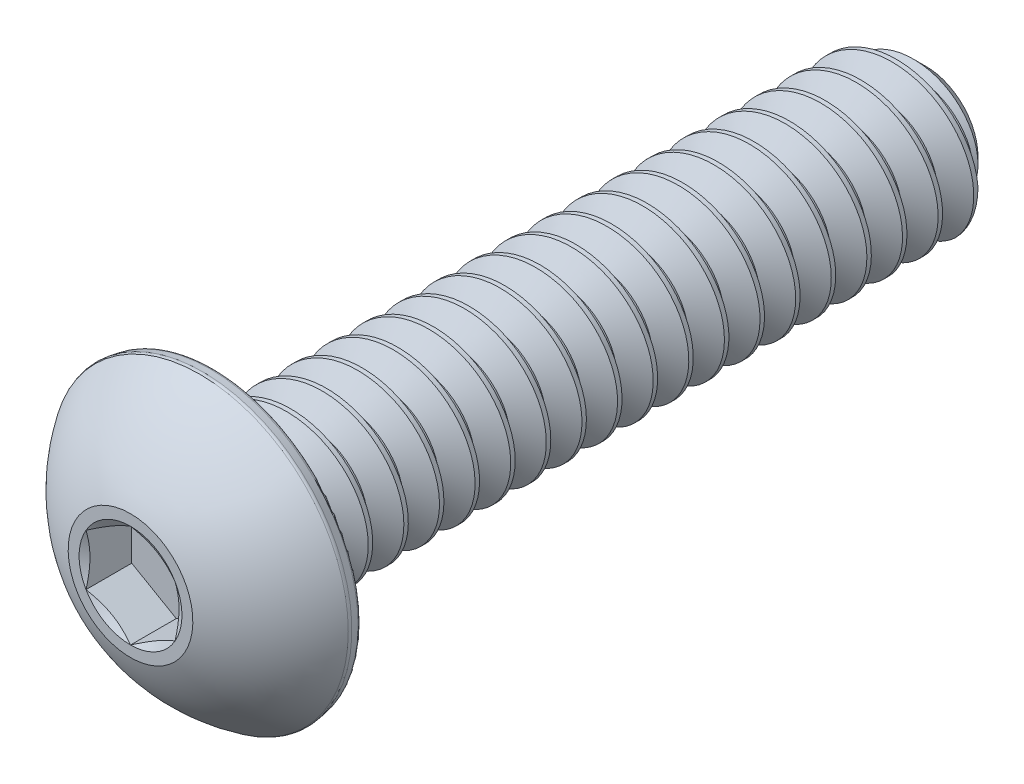
SolidWorks part; units mm, degrees
ref_plane "Front Plane" through (0, 0, 0) normal (0, 0, 1) x (1, 0, 0)
ref_plane "Top Plane" through (0, 0, 0) normal (0, 1, 0) x (1, 0, 0)
ref_plane "Right Plane" through (0, 0, 0) normal (1, 0, 0) x (0, 0, -1)
sketch "Sketch1" plane through (0, 0, 0) normal (1, 0, 0) x (0, 0, -1)
  line L0 (-8.8646, 0) -> (8.8646, 0) construction
  line L1 (-8.8646, 0) -> (-8.8646, 3.3274)
  line L2 (-8.8646, 3.3274) -> (-7.0104, 3.3274)
  line L3 (-7.0104, 3.3274) -> (-7.0104, 1.7526)
  line L4 (-7.0104, 1.7526) -> (8.8646, 1.7526)
  line L5 (8.8646, 1.7526) -> (8.8646, 0)
  point P2 (0, 0)
  point P4 (8.0709, 0)
  point P9 (7.674, 1.7526)
  point P10 (7.674, -1.7526)
  point P11 (8.8646, -1.7526)
  point P15 (-7.8448, 0)
  dimension "Head Height" = 1.8542
  dimension "Head Diameter" = 6.6548
  dimension "Length" = 15.875
  dimension "Screw Size Decimal Equivalent" = 3.5052
  dimension "Thread Pitch" = 0.7937
  dimension "D1" = 1.1906
  dimension "D2" = 1.0198
sketch "Sketch2" plane through (0, 0, 0) normal (0, 0, 1) x (1, 0, 0)
  line L0 (0, 1.7526) -> (0, 0) construction
  line L1 (0, 1.1457) -> (-0.9922, 0.5728)
  line L2 (-0.9922, 0.5728) -> (-0.9922, -0.5728)
  line L3 (-0.9922, -0.5728) -> (0, -1.1457)
  line L4 (0, -1.1457) -> (0.9922, -0.5728)
  line L5 (0.9922, -0.5728) -> (0.9922, 0.5728)
  line L6 (0.9922, 0.5728) -> (0, 1.1457)
  circle A0 centre (0, 0) radius 0.9922 construction
  circle A1 centre (0, 0) radius 1.3891
  point P10 (0, 1.3891)
  dimension "D1" = 2.7781
  dimension "Drive Size" = 1.9844
sketch "Sketch3" plane through (0, 0, 0) normal (1, 0, 0) x (0, 0, -1)
  line L0 (-8.8646, 0) -> (-8.8646, 1.3891)
  line L1 (-8.8646, 0) -> (-8.8646, 3.3274) construction
  line L2 (-8.8646, 3.3274) -> (-7.0104, 3.3274) construction
  line L3 (-7.2885, 3.3274) -> (-7.0104, 3.2784)
  line L4 (-7.0104, 3.3274) -> (-7.0104, 1.7526) construction
  line L5 (-7.0104, 3.2784) -> (-7.0104, 1.7526)
  line L6 (-8.8646, 0) -> (8.8646, 0) construction
  line L7 (-8.8646, 0) -> (8.8646, 0)
  line L8 (8.8646, 0) -> (8.8646, 1.1573)
  line L9 (8.8646, 1.7526) -> (8.8646, 0) construction
  line L10 (8.8646, 1.1573) -> (8.2693, 1.7526)
  line L11 (-7.0104, 1.7526) -> (8.8646, 1.7526) construction
  line L12 (8.2693, 1.7526) -> (-7.0104, 1.7526)
  arc A0 (-8.8646, 1.3891) -> (-7.2885, 3.3274) centre (-5.1763, 0) cw
  dimension "D1" = 0.2781
  dimension "D2" = 10
  dimension "D3" = 45
  dimension "D4" = 0.5953
revolve "Revolve1" add sketch "Sketch3" angle 360 about L7
sketch "Sketch4" plane through (0, 0, 8.8646) normal (0, 0, 1) x (1, 0, 0)
  line L0 (-0.9922, -0.5728) -> (0, -1.1457) construction
  line L1 (-0.9922, 0.5728) -> (-0.9922, -0.5728) construction
  line L2 (0, 1.1457) -> (-0.9922, 0.5728) construction
  line L3 (0.9922, 0.5728) -> (0, 1.1457) construction
  line L4 (0.9922, -0.5728) -> (0.9922, 0.5728) construction
  line L5 (0, -1.1457) -> (0.9922, -0.5728) construction
  line L6 (-0.9922, -0.5728) -> (0, -1.1457)
  line L7 (-0.9922, 0.5728) -> (-0.9922, -0.5728)
  line L8 (0, 1.1457) -> (-0.9922, 0.5728)
  line L9 (0.9922, 0.5728) -> (0, 1.1457)
  line L10 (0.9922, -0.5728) -> (0.9922, 0.5728)
  line L11 (0, -1.1457) -> (0.9922, -0.5728)
extrude "Cut-Extrude1" cut sketch "Sketch4" against normal up to vertex (1.0198 mm away) up to point (0, 0, 7.8448)
sketch "Sketch5" plane through (0, 0, 8.8646) normal (0, 0, 1) x (1, 0, 0)
  circle A0 centre (0, 0) radius 1.1457
extrude "Cut-Extrude2" cut sketch "Sketch5" against normal up to vertex (1.0198 mm away) draft 60 up to point (0, 0, 7.8448)
fillet "Fillet1" radius 0.0927 2 edges at (3.3274, 0, 7.2885) (3.2784, 0, 7.0104)
split "Split1" bodies to split 106 resulting bodies 107 108 split by face at (3.2006, 0, 7.0104)
sketch "Sketch6" plane through (0, 0, -8.8646) normal (0, 0, -1) x (-1, 0, 0)
  circle A0 centre (0, 0) radius 1.7526 construction
  circle A1 centre (0, 0) radius 1.7526
curve "Helix/Spiral1" pitch 0.7937 height 16.6687 radius 1.7526 centre (0, 0, -8.8646) axis (0, 0, 1) start towards (0, 1, 0)
sketch "Sketch7" plane through (0, 0, 0) normal (1, 0, 0) x (0, 0, -1)
  line L0 (8.815, 1.8385) -> (9.2119, 1.1511) construction
  line L1 (9.2119, 1.1511) -> (9.6087, 1.8385) construction
  line L2 (9.6087, 1.8385) -> (8.815, 1.8385) construction
  line L3 (8.8398, 1.7956) -> (9.5839, 1.7956)
  line L4 (9.5839, 1.7956) -> (9.2615, 1.237)
  line L5 (9.2615, 1.237) -> (9.1623, 1.237)
  line L6 (9.1623, 1.237) -> (8.8398, 1.7956)
  line L7 (9.2119, 1.237) -> (9.2119, 1.1511) construction
  line L8 (8.8646, 1.7526) -> (9.5591, 1.7526) construction
  line L9 (9.2119, 1.8385) -> (9.2119, 1.7526) construction
  point P12 (9.2119, 1.7956)
  dimension "D1" = 0.7937
  dimension "D2" = 0.0992
sweep "Cut-Sweep1" cut profiles "Sketch7" path "Helix/Spiral1" align with end faces yes
sketch "Sketch8" plane through (0, 0, 7.0104) normal (0, 0, -1) x (-1, 0, 0)
  circle A0 centre (0, 0) radius 1.8385
extrude "Boss-Extrude1" add sketch "Sketch8" along normal up to vertex (14.6844 mm away) draft 45 up to point (0, 1.7526, -7.674)
equation "\"D1@Sketch1\"=\"Thread Pitch@Sketch1\"*1.5"
equation "\"D2@Sketch1\"=0.55*\"Head Height@Sketch1\""
equation "\"D1@Sketch2\"=\"Drive Size@Sketch2\"*1.4"
equation "\"D1@Sketch3\"=0.15*\"Head Height@Sketch1\""
equation "\"D4@Sketch3\"=0.75*\"Thread Pitch@Sketch1\""
equation "\"D1@Fillet1\"=.05*\"Head Height@Sketch1\""
equation "\"D4@Helix/Spiral1\"=\"Thread Pitch@Sketch1\""
equation "\"D3@Helix/Spiral1\"=\"Length@Sketch1\"+\"Thread Pitch@Sketch1\""
equation "\"D2@Sketch7\"=\"D1@Sketch7\"/8"
equation "\"D1@Sketch7\"=\"Thread Pitch@Sketch1\""
